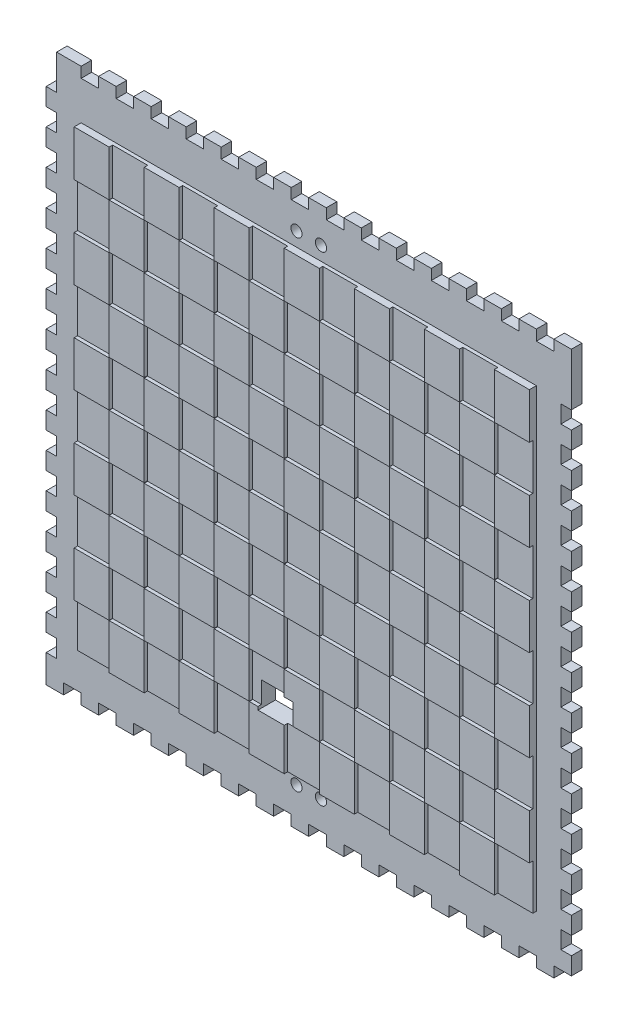
SolidWorks part; units mm, degrees
ref_plane "Front Plane" through (0, 0, 0) normal (0, 0, 1) x (1, 0, 0)
ref_plane "Top Plane" through (0, 0, 0) normal (0, 1, 0) x (1, 0, 0)
ref_plane "Right Plane" through (0, 0, 0) normal (1, 0, 0) x (0, 0, -1)
sketch "Sketch1" plane through (0, 0, 0) normal (0, 0, 1) x (1, 0, 0)
  line L1 (-75, 79) -> (75, 79)
  line L2 (-75, 79) -> (-75, -79)
  line L3 (-75, -79) -> (75, -79)
  line L4 (75, 79) -> (75, -79)
  line L5 (-75, 79) -> (75, -79) construction
  line L6 (-75, -79) -> (75, 79) construction
  point P0 (0, 0)
  dimension "D1" = 158
  dimension "D2" = 150
extrude "Boss-Extrude1" add sketch "Sketch1" along normal blind 5
sketch "Sketch2" plane through (0, 0, 5) normal (0, 0, 1) x (1, 0, 0)
  line L1 (-65, 65) -> (65, 65)
  line L2 (-65, 65) -> (-65, -65)
  line L3 (-65, -65) -> (65, -65)
  line L4 (65, 65) -> (65, -65)
  line L5 (-65, 65) -> (65, -65) construction
  line L6 (-65, -65) -> (65, 65) construction
  line L7 (-75, 79) -> (75, 79)
  line L8 (-75, 79) -> (-75, -79)
  line L9 (-75, -79) -> (75, -79)
  line L10 (75, 79) -> (75, -79)
  line L11 (-75, 79) -> (75, -79) construction
  line L12 (-75, -79) -> (75, 79) construction
  point P0 (0, 0)
  point P6 (0, 0)
  dimension "D1" = 130
  dimension "D2" = 130
extrude "Cut-Extrude1" cut sketch "Sketch2" against normal blind 2
sketch "Sketch3" plane through (0, 0, 5) normal (0, 0, 1) x (1, 0, 0)
  line L0 (-65, 65) -> (-65, -65) construction
  line L1 (-65, 51.95) -> (-55, 51.95)
  line L2 (-65, 51.95) -> (-65, 38.85)
  line L3 (-65, 38.85) -> (-55, 38.85)
  line L4 (-55, 51.95) -> (-55, 38.85)
  dimension "D1" = 13.1
  dimension "D2" = 10
  dimension "D3" = 13.05
extrude "Cut-Extrude2" cut sketch "Sketch3" against normal blind 1
pattern_linear "LPattern1" count 7 spacing 20 along (1, 0, 0) count 5 spacing 26 along (0, -1, 0) of "Cut-Extrude2"
sketch "Sketch4" plane through (0, 0, 5) normal (0, 0, 1) x (1, 0, 0)
  line L0 (65, 65) -> (-65, 65) construction
  line L1 (-55, 65) -> (-45, 65)
  line L2 (-55, 65) -> (-55, 51.9)
  line L3 (-55, 51.9) -> (-45, 51.9)
  line L4 (-45, 65) -> (-45, 51.9)
  line L5 (-65, 65) -> (-65, 51.95) construction
  dimension "D1" = 13.1
  dimension "D2" = 10
  dimension "D3" = 10
extrude "Cut-Extrude3" cut sketch "Sketch4" against normal blind 1
pattern_linear "LPattern2" count 6 spacing 20 along (1, 0, 0) count 5 spacing 26 along (0, -1, 0) of "Cut-Extrude3"
sketch "Sketch5" plane through (0, 0, 3) normal (0, 0, 1) x (1, 0, 0)
  line L0 (75, 79) -> (-75, 79) construction
  line L1 (-65, 79) -> (-60, 79)
  line L2 (-65, 79) -> (-65, 76)
  line L3 (-65, 76) -> (-60, 76)
  line L4 (-60, 79) -> (-60, 76)
  line L5 (-75, 79) -> (-75, -79) construction
  line L6 (-55, 79) -> (-55, 76)
  line L7 (-55, 79) -> (-50, 79)
  line L8 (-50, 79) -> (-50, 76)
  line L9 (-55, 76) -> (-50, 76)
  line L10 (-45, 79) -> (-45, 76)
  line L11 (-45, 79) -> (-40, 79)
  line L12 (-40, 79) -> (-40, 76)
  line L13 (-45, 76) -> (-40, 76)
  line L14 (-35, 79) -> (-35, 76)
  line L15 (-35, 79) -> (-30, 79)
  line L16 (-30, 79) -> (-30, 76)
  line L17 (-35, 76) -> (-30, 76)
  line L18 (-25, 79) -> (-25, 76)
  line L19 (-25, 79) -> (-20, 79)
  line L20 (-20, 79) -> (-20, 76)
  line L21 (-25, 76) -> (-20, 76)
  line L22 (-15, 79) -> (-15, 76)
  line L23 (-15, 79) -> (-10, 79)
  line L24 (-10, 79) -> (-10, 76)
  line L25 (-15, 76) -> (-10, 76)
  line L26 (-5, 79) -> (-5, 76)
  line L27 (-5, 79) -> (0, 79)
  line L28 (0, 79) -> (0, 76)
  line L29 (-5, 76) -> (0, 76)
  line L30 (5, 79) -> (5, 76)
  line L31 (5, 79) -> (10, 79)
  line L32 (10, 79) -> (10, 76)
  line L33 (5, 76) -> (10, 76)
  line L34 (15, 79) -> (15, 76)
  line L35 (15, 79) -> (20, 79)
  line L36 (20, 79) -> (20, 76)
  line L37 (15, 76) -> (20, 76)
  line L38 (25, 79) -> (25, 76)
  line L39 (25, 79) -> (30, 79)
  line L40 (30, 79) -> (30, 76)
  line L41 (25, 76) -> (30, 76)
  line L42 (35, 79) -> (35, 76)
  line L43 (35, 79) -> (40, 79)
  line L44 (40, 79) -> (40, 76)
  line L45 (35, 76) -> (40, 76)
  line L46 (45, 79) -> (45, 76)
  line L47 (45, 79) -> (50, 79)
  line L48 (50, 79) -> (50, 76)
  line L49 (45, 76) -> (50, 76)
  line L50 (55, 79) -> (55, 76)
  line L51 (55, 79) -> (60, 79)
  line L52 (60, 79) -> (60, 76)
  line L53 (55, 76) -> (60, 76)
  line L54 (65, 79) -> (65, 76)
  line L55 (65, 79) -> (70, 79)
  line L56 (70, 79) -> (70, 76)
  line L57 (65, 76) -> (70, 76)
  line L62 (75, 79) -> (75, 76) [skipped]
  line L63 (75, 79) -> (80, 79) [skipped]
  line L64 (80, 79) -> (80, 76) [skipped]
  line L65 (75, 76) -> (80, 76) [skipped]
  dimension "D1" = 10
  dimension "D2" = 5
  dimension "D3" = 3
  dimension "D4" = 15
extrude "Cut-Extrude4" cut sketch "Sketch5" against normal through all
sketch "Sketch6" plane through (0, 0, 3) normal (0, 0, 1) x (1, 0, 0)
  line L1 (-75, 79) -> (-72, 79)
  line L2 (-75, 79) -> (-75, 69)
  line L3 (-75, 69) -> (-72, 69)
  line L4 (-72, 79) -> (-72, 69)
  dimension "D1" = 10
  dimension "D2" = 3
extrude "Cut-Extrude5" cut sketch "Sketch6" against normal through all
sketch "Sketch7" plane through (0, 0, 3) normal (0, 0, 1) x (1, 0, 0)
  line L0 (-75, 69) -> (-75, -79) construction
  line L1 (-75, 64) -> (-72, 64)
  line L2 (-75, 64) -> (-75, 59)
  line L3 (-75, 59) -> (-72, 59)
  line L4 (-72, 64) -> (-72, 59)
  line L5 (-75, 69) -> (-72, 69) construction
  dimension "D1" = 5
  dimension "D2" = 5
  dimension "D3" = 3
extrude "Cut-Extrude6" cut sketch "Sketch7" against normal through all
pattern_linear "LPattern3" count 14 spacing 10 along (0, -1, 0) of "Cut-Extrude6"
sketch "Sketch8" plane through (0, 0, 3) normal (0, 0, 1) x (1, 0, 0)
  line L0 (-75, -79) -> (75, -79) construction
  line L1 (-70, -79) -> (-65, -79)
  line L2 (-70, -79) -> (-70, -76)
  line L3 (-70, -76) -> (-65, -76)
  line L4 (-65, -79) -> (-65, -76)
  line L5 (-75, -71) -> (-75, -79) construction
  dimension "D1" = 3
  dimension "D2" = 5
  dimension "D3" = 5
extrude "Cut-Extrude7" cut sketch "Sketch8" against normal through all
pattern_linear "LPattern4" count 15 spacing 10 along (1, 0, 0) of "Cut-Extrude7"
sketch "Sketch9" plane through (0, 0, 3) normal (0, 0, 1) x (1, 0, 0)
  line L0 (75, -76) -> (75, 79) construction
  line L1 (75, -71) -> (72, -71)
  line L2 (75, -71) -> (75, -66)
  line L3 (75, -66) -> (72, -66)
  line L4 (72, -71) -> (72, -66)
  line L5 (75, -76) -> (70, -76) construction
  dimension "D1" = 5
  dimension "D2" = 5
  dimension "D3" = 3
extrude "Cut-Extrude8" cut sketch "Sketch9" against normal blind 10
pattern_linear "LPattern5" count 14 spacing 10 along (0, 1, 0) of "Cut-Extrude8"
sketch "Sketch10" plane through (0, 0, 3) normal (0, 0, 1) x (1, 0, 0)
  line L0 (65, 65) -> (-65, 65) construction
  line L2 (-5, 76) -> (0, 76) construction
  line L3 (5, 76) -> (10, 76) construction
  circle A0 centre (-3.5, 69) radius 1.6
  circle A1 centre (3.5, 69) radius 1.6
  point P6 (0, 65)
  dimension "D1" = 3.2
  dimension "D2" = 3.2
  dimension "D3" = 3.5
  dimension "D4" = 3.5
  dimension "D5" = 7
  dimension "D6" = 7
extrude "Cut-Extrude9" cut sketch "Sketch10" against normal blind 15
sketch "Sketch12" plane through (0, 0, 3) normal (0, 0, 1) x (1, 0, 0)
  line L0 (-5, -76) -> (-10, -76) construction
  line L1 (5, -76) -> (0, -76) construction
  circle A0 centre (3.5, -68) radius 1.6
  circle A1 centre (-3.5, -68) radius 1.6
  dimension "D1" = 3.2
  dimension "D2" = 3.2
  dimension "D3" = 3.5
  dimension "D4" = 3.5
  dimension "D5" = 8
  dimension "D6" = 8
extrude "Cut-Extrude10" cut sketch "Sketch12" against normal blind 10
sketch "Sketch13" plane through (0, 0, 0) normal (1, 0, 0) x (0, 0, -1)
  line L0 (0, -26) -> (0, -21) construction
  line L1 (0, -44) -> (4, -44)
  line L2 (0, -44) -> (0, -46)
  line L3 (0, -46) -> (4, -46)
  line L4 (4, -44) -> (4, -46)
  line L5 (0, -76) -> (-3, -76) construction
  dimension "D1" = 30
  dimension "D2" = 2
  dimension "D3" = 4
extrude "Boss-Extrude2" add sketch "Sketch13" against normal offset from surface 4 and the other way blind 12 up to face at (-72, -48.5, 1.5)
sketch "Sketch14" plane through (0, -44, 0) normal (0, 1, 0) x (1, 0, 0)
  line L0 (-68, 0) -> (-68, 4) construction
  line L1 (-68, 4) -> (12, 4) construction
  line L2 (-32, 14.2038) -> (-32, -17.5548) construction
  line L3 (12, 4) -> (12, 0) construction
  line L4 (12, 4) -> (-68, 4) construction
  circle A1 centre (-33.9, 2.1) radius 1
  circle A2 centre (-30.1, 2.1) radius 1
  circle A3 centre (6.1, 2.1) radius 1.1052
  dimension "D5" = 2
  dimension "D8" = 2
  dimension "D9" = 2.2104
  dimension "D4" = 36
  dimension "D6" = 1.9
  dimension "D7" = 1.9
  dimension "D10" = 5.9
  dimension "D11" = 1.9
  dimension "D12" = 1.9
  dimension "D13" = 1.9
extrude "Cut-Extrude11" cut sketch "Sketch14" against normal blind 4
sketch "Sketch15" plane through (0, 0, 0) normal (0, 0, -1) x (-1, 0, 0)
  line L1 (2.5, -46) -> (12.5, -46)
  line L2 (2.5, -46) -> (2.5, -53)
  line L3 (2.5, -53) -> (12.5, -53)
  line L4 (12.5, -46) -> (12.5, -53)
  line L5 (-12, -44) -> (-12, -46) construction
  line L6 (-12, -46) -> (68, -46) construction
  dimension "D1" = 7
  dimension "D2" = 10
  dimension "D4" = 14.5
extrude "Cut-Extrude12" cut sketch "Sketch15" against normal through all
sketch "Sketch16" plane through (0, 0, 0) normal (1, 0, 0) x (0, 0, -1)
  line L0 (0, -36) -> (0, -31) construction
  line L1 (0, -27) -> (4, -27)
  line L2 (0, -27) -> (0, -29)
  line L3 (0, -29) -> (4, -29)
  line L4 (4, -27) -> (4, -29)
  line L5 (4, -44) -> (0, -44) construction
  dimension "D1" = 2
  dimension "D2" = 4
  dimension "D3" = 15
extrude "Boss-Extrude3" add sketch "Sketch16" against normal offset from surface (68 mm away) 4 up to face at (-72, -38.5, 1.5)
sketch "Sketch17" plane through (0, -27, 0) normal (0, 1, 0) x (1, 0, 0)
  circle A0 centre (-33.9, 2.1) radius 1 construction
  circle A1 centre (-33.9, 2.1) radius 1
extrude "Cut-Extrude13" cut sketch "Sketch17" against normal through all
